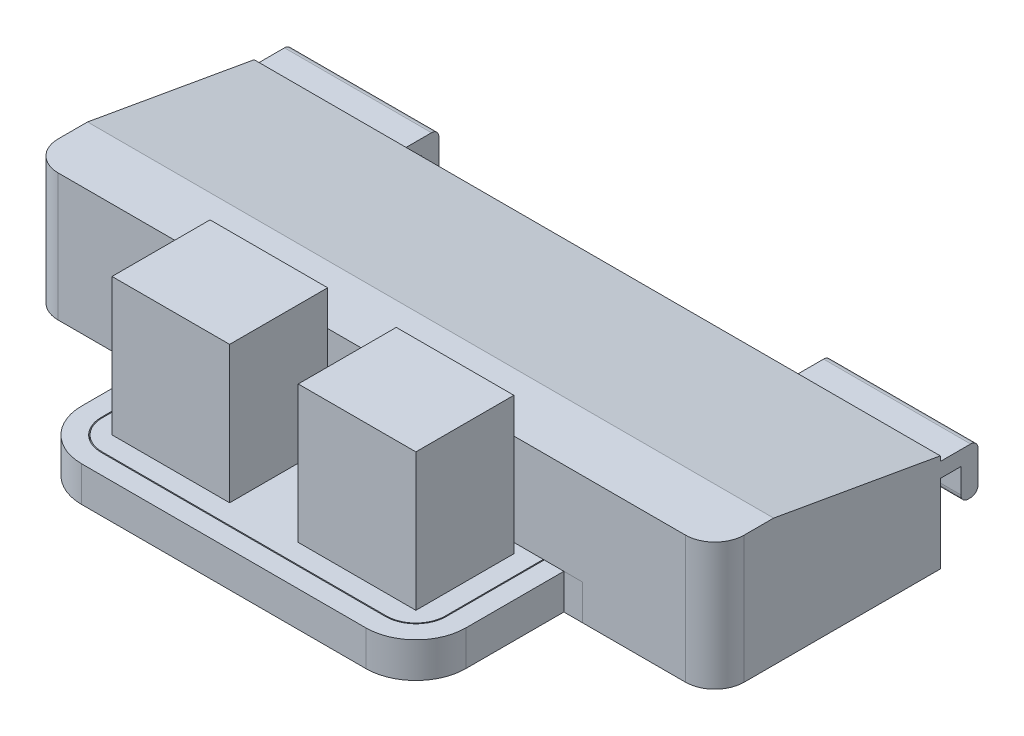
SolidWorks part; units mm, degrees
ref_plane "Front Plane" through (0, 0, 0) normal (0, 0, 1) x (1, 0, 0)
ref_plane "Top Plane" through (0, 0, 0) normal (0, 1, 0) x (1, 0, 0)
ref_plane "Right Plane" through (0, 0, 0) normal (1, 0, 0) x (0, 0, -1)
sketch "Sketch1" plane through (0, 0, 0) normal (0, 1, 0) x (1, 0, 0)
  line L0 (-17.5, 0) -> (-17.5, 15)
  line L1 (-17.5, 15) -> (-24.5, 15)
  line L2 (-24.5, 15) -> (-24.5, 30)
  line L3 (-24.5, 30) -> (24.5, 30)
  line L4 (24.5, 30) -> (24.5, 15)
  line L5 (24.5, 15) -> (17.5, 15)
  line L6 (17.5, 15) -> (17.5, 0)
  line L7 (17.5, 0) -> (-17.5, 0)
  line L8 (0, 0) -> (0, 30) construction
  point P2 (0, 0)
  dimension "D1" = 35
  dimension "D2" = 49
  dimension "D3" = 15
  dimension "D4" = 30
extrude "Boss-Extrude1" add sketch "Sketch1" along normal blind 1.6
sketch "Sketch2" plane through (0, 1.6, 0) normal (0, 1, 0) x (1, 0, 0)
  line L0 (0, 30) -> (0, 25.132) construction
  line L1 (24.5, 30) -> (-24.5, 30) construction
  line L2 (-24.5, 22.5) -> (-16.8448, 22.5) construction
  line L3 (-24.5, 30) -> (-24.5, 15) construction
  line L4 (-24.5, 15) -> (-17.5, 15) construction
  circle A0 centre (-20.5, 26) radius 1.5
  circle A1 centre (-20.5, 19) radius 1.5
  circle A2 centre (20.5, 26) radius 1.5
  circle A3 centre (20.5, 19) radius 1.5
  dimension "D1" = 3
  dimension "D2" = 4
  dimension "D3" = 4
extrude "Cut-Extrude1" cut sketch "Sketch2" against normal through all
fillet "Fillet1" radius 3 6 edges at (-17.5, 0.8, 0) (17.5, 0.8, 0) (24.5, 0.8, -15) (24.5, 0.8, -30) (-24.5, 0.8, -30) (-24.5, 0.8, -15)
sketch "Sketch3" plane through (0, 1.6, 0) normal (0, 1, 0) x (1, 0, 0)
  line L0 (0, 0) -> (0, 14.2709) construction
  line L1 (-14.5, 0) -> (14.5, 0) construction
  line L2 (15.5, 2) -> (3.5, 12) construction
  line L3 (-15.5, 12) -> (-3.5, 12)
  line L4 (-15.5, 12) -> (-15.5, 2)
  line L5 (-15.5, 2) -> (-3.5, 2)
  line L6 (-3.5, 12) -> (-3.5, 2)
  line L7 (-15.5, 12) -> (-3.5, 2) construction
  line L8 (-15.5, 2) -> (-3.5, 12) construction
  line L9 (15.5, 12) -> (3.5, 2) construction
  line L10 (3.5, 12) -> (3.5, 2)
  line L11 (15.5, 2) -> (3.5, 2)
  line L12 (15.5, 12) -> (15.5, 2)
  line L13 (15.5, 12) -> (3.5, 12)
  point P4 (-9.5, 7)
  point P13 (9.5, 7)
  dimension "D1" = 12
  dimension "D2" = 10
  dimension "D3" = 19
  dimension "D4" = 7
extrude "Boss-Extrude2" add sketch "Sketch3" along normal blind 14
sketch "Sketch4" plane through (0, 0, 0) normal (0, -1, 0) x (1, 0, 0)
  line L3 (0, -30) -> (0, -13) construction
  line L4 (-32, -13) -> (-19.6, -13)
  line L5 (-35, -16) -> (-35, -35)
  line L6 (19.6, -3) -> (19.6, -15)
  line L7 (-14.5, 2.1) -> (14.5, 2.1)
  line L8 (-19.6, -15) -> (-19.6, -3)
  line L9 (19.6, -3) -> (19.6, -13)
  line L10 (-14.5, 2.1) -> (14.5, 2.1)
  line L11 (-19.6, -13) -> (-19.6, -3)
  line L12 (-35, -35) -> (35, -35)
  line L13 (35, -16) -> (35, -35)
  line L14 (21.5, -30) -> (-21.5, -30) construction
  line L15 (-24.5, -27) -> (-24.5, -18) construction
  line L16 (-21.5, -15) -> (-17.5, -15) construction
  line L17 (19.6, -13) -> (32, -13)
  arc A2 (32, -13) -> (35, -16) centre (32, -16) cw
  arc A3 (-32, -13) -> (-35, -16) centre (-32, -16) ccw
  arc A4 (19.6, -3) -> (14.5, 2.1) centre (14.5, -3) ccw
  arc A5 (-14.5, 2.1) -> (-19.6, -3) centre (-14.5, -3) ccw
  arc A6 (19.6, -3) -> (14.5, 2.1) centre (14.5, -3) ccw
  arc A7 (-14.5, 2.1) -> (-19.6, -3) centre (-14.5, -3) ccw
  dimension "D5" = 3
  dimension "D2" = 10.5
  dimension "D3" = 2
  dimension "D4" = 5
  dimension "D6" = 70
  dimension "D1" = 2.1
extrude "Boss-Extrude3" add sketch "Sketch4" along normal blind 2 separate body
sketch "Sketch5" plane through (0, 0, 0) normal (0, 1, 0) x (1, 0, 0)
  line L8 (35, 16) -> (35, 35)
  line L9 (35, 35) -> (-35, 35)
  line L10 (-35, 35) -> (-35, 16)
  line L11 (-32, 13) -> (-19.6, 13)
  line L12 (-19.6, 13) -> (-19.6, 3)
  line L13 (-14.5, -2.1) -> (14.5, -2.1)
  line L14 (19.6, 3) -> (19.6, 13)
  line L15 (19.6, 13) -> (32, 13)
  line L19 (-21.5, 13) -> (-19.6, 13)
  line L20 (-19.6, 13) -> (-19.6, 3)
  line L21 (-14.5, -2.1) -> (14.5, -2.1)
  line L22 (19.6, 3) -> (19.6, 13)
  line L23 (19.6, 13) -> (21.5, 13)
  line L28 (-21.5, 14.9) -> (-21.5, 13)
  line L29 (21.5, 14.9) -> (21.5, 13)
  line L33 (-21.5, 14.9) -> (-17.6, 14.9)
  line L34 (17.6, 14.9) -> (21.5, 14.9)
  line L35 (-17.6, 14.9) -> (-17.6, 3)
  line L36 (-14.5, -0.1) -> (14.5, -0.1)
  line L37 (17.6, 3) -> (17.6, 14.9)
  line L38 (-21.5, 14.9) -> (-17.6, 14.9)
  line L39 (17.6, 14.9) -> (21.5, 14.9)
  line L40 (-17.6, 14.9) -> (-17.6, 3)
  line L41 (-14.5, -0.1) -> (14.5, -0.1)
  line L42 (17.6, 3) -> (17.6, 14.9)
  arc A4 (-35, 16) -> (-32, 13) centre (-32, 16) ccw
  arc A5 (-19.6, 3) -> (-14.5, -2.1) centre (-14.5, 3) ccw
  arc A6 (14.5, -2.1) -> (19.6, 3) centre (14.5, 3) ccw
  arc A7 (32, 13) -> (35, 16) centre (32, 16) ccw
  arc A9 (-19.6, 3) -> (-14.5, -2.1) centre (-14.5, 3) ccw
  arc A10 (14.5, -2.1) -> (19.6, 3) centre (14.5, 3) ccw
  arc A16 (-17.6, 3) -> (-14.5, -0.1) centre (-14.5, 3) ccw
  arc A17 (14.5, -0.1) -> (17.6, 3) centre (14.5, 3) ccw
  arc A18 (-17.6, 3) -> (-14.5, -0.1) centre (-14.5, 3) ccw
  arc A19 (14.5, -0.1) -> (17.6, 3) centre (14.5, 3) ccw
  dimension "D1" = 0
  dimension "D2" = 0.1
extrude "Boss-Extrude4" add sketch "Sketch5" along normal up to surface (1.6 mm away) separate body up to face at (-9.5, 1.6, -7)
sketch "Sketch6" plane through (0, 0, 0) normal (0, 1, 0) x (1, 0, 0)
  line L0 (-35, 16) -> (-35, 35) construction
  line L1 (-19.6, 13) -> (-32, 13) construction
  line L2 (32, 13) -> (19.6, 13) construction
  line L3 (35, 35) -> (35, 16) construction
  line L4 (-35, 16) -> (-35, 35)
  line L5 (-21.5, 13) -> (-32, 13)
  line L6 (32, 13) -> (21.5, 13)
  line L7 (35, 35) -> (35, 16)
  line L8 (-21.5, 14) -> (-32, 14)
  line L9 (-34, 16) -> (-34, 35)
  line L10 (34, 35) -> (34, 16)
  line L11 (32, 14) -> (21.5, 14)
  line L12 (-21.5, 13) -> (-21.5, 14.9) construction
  line L13 (21.5, 14.9) -> (21.5, 13) construction
  line L14 (-21.5, 13) -> (-21.5, 14)
  line L15 (21.5, 14) -> (21.5, 13)
  line L16 (35, 35) -> (34, 35)
  line L17 (-19.6, 13) -> (-32, 13) construction
  line L18 (-19.6, 14) -> (-32, 14) construction
  line L19 (32, 13) -> (19.6, 13) construction
  line L20 (32, 14) -> (19.6, 14) construction
  line L21 (-34, 35) -> (-35, 35)
  arc A0 (-35, 16) -> (-32, 13) centre (-32, 16) ccw construction
  arc A1 (32, 13) -> (35, 16) centre (32, 16) ccw construction
  arc A2 (-35, 16) -> (-32, 13) centre (-32, 16) ccw
  arc A3 (32, 13) -> (35, 16) centre (32, 16) ccw
  arc A4 (-34, 16) -> (-32, 14) centre (-32, 16) ccw
  arc A5 (32, 14) -> (34, 16) centre (32, 16) ccw
  dimension "D1" = 1
extrude "Cut-Extrude2" cut sketch "Sketch6" against normal through all
sketch "Sketch7" plane through (0, -2, 0) normal (0, -1, 0) x (1, 0, 0)
  line L5 (-34, -16) -> (-34, -35) construction
  line L6 (-21.5, -14) -> (-32, -14) construction
  line L7 (-34, -35) -> (34, -35) construction
  line L8 (34, -35) -> (34, -16) construction
  line L9 (32, -14) -> (21.5, -14) construction
  line L10 (-21.5, -13) -> (-32, -13)
  line L11 (-35, -16) -> (-35, -36)
  line L12 (-35, -36) -> (35, -36)
  line L13 (32, -13) -> (21.5, -13)
  line L14 (35, -36) -> (35, -16)
  line L15 (-21.5, -13) -> (-32, -13)
  line L16 (-35, -16) -> (-35, -36)
  line L17 (-35, -36) -> (35, -36)
  line L18 (32, -13) -> (21.5, -13)
  line L19 (35, -36) -> (35, -16)
  line L20 (-34, -16) -> (-34, -35)
  line L21 (-21.5, -14) -> (-32, -14)
  line L22 (-34, -35) -> (34, -35)
  line L23 (34, -35) -> (34, -16)
  line L24 (32, -14) -> (21.5, -14)
  line L25 (21.5, -14) -> (21.5, -13)
  line L26 (-21.5, -14) -> (-21.5, -13)
  arc A2 (-32, -14) -> (-34, -16) centre (-32, -16) ccw construction
  arc A3 (34, -16) -> (32, -14) centre (32, -16) ccw construction
  arc A4 (-32, -13) -> (-35, -16) centre (-32, -16) ccw
  arc A5 (35, -16) -> (32, -13) centre (32, -16) ccw
  arc A6 (-32, -13) -> (-35, -16) centre (-32, -16) ccw
  arc A7 (35, -16) -> (32, -13) centre (32, -16) ccw
  arc A8 (-32, -14) -> (-34, -16) centre (-32, -16) ccw
  arc A9 (34, -16) -> (32, -14) centre (32, -16) ccw
  dimension "D1" = 1
extrude "Boss-Extrude5" add sketch "Sketch7" against normal blind 15 separate body
sketch "Sketch8" plane through (0, 0, 0) normal (1, 0, 0) x (0, 0, -1)
  line L0 (36, 8) -> (19, 11)
  line L1 (36, 13) -> (36, -2) construction
  line L2 (19, 11) -> (13, 11)
  line L3 (13, 13) -> (13, -2) construction
  line L4 (13, 11) -> (13, 13)
  line L5 (13, 13) -> (36, 13)
  line L6 (36, 13) -> (36, 8)
  line L7 (16, -2) -> (36, -2) construction
  dimension "D1" = 10
  dimension "D2" = 2
  dimension "D3" = 6
extrude "Cut-Extrude3" cut sketch "Sketch8" against normal through all both and the other way through all
sketch "Sketch9" plane through (0, 0, 0) normal (1, 0, 0) x (0, 0, -1)
  line L0 (35, 8.1765) -> (19, 11)
  line L1 (19, 11) -> (14, 11)
  line L2 (14, 11) -> (14, 9.46)
  line L3 (14, 11) -> (14, -2) construction
  line L4 (14, 9.46) -> (19.0953, 9.46)
  line L5 (19.0953, 9.46) -> (35, 6.6533)
  line L6 (35, 8.1765) -> (35, -2) construction
  line L7 (35, 6.6533) -> (35, 8.1765)
  dimension "D1" = 1.54
  dimension "D2" = 1.5
extrude "Boss-Extrude6" add sketch "Sketch9" along normal up to next and the other way up to next
sketch "Sketch10" plane through (0, 11, 0) normal (0, 1, 0) x (1, 0, 0)
  line L1 (21.5, 13) -> (-21.5, 13)
  line L2 (21.5, 13) -> (21.5, 14)
  line L3 (21.5, 14) -> (-21.5, 14)
  line L4 (-21.5, 13) -> (-21.5, 14)
  line L5 (-21.5, 14) -> (21.5, 14) construction
  line L6 (-21.5, 13) -> (-21.5, 14) construction
extrude "Boss-Extrude7" add sketch "Sketch10" against normal up to surface (9.4 mm away) separate body up to face at (-9.5, 1.6, -7)
sketch "Sketch11" plane through (0, 0, -36) normal (0, 0, -1) x (-1, 0, 0)
  line L0 (-20, 1.6) -> (20, 1.6) construction
  line L1 (-21.5, 1.6) -> (21.5, 1.6) construction
  line L2 (-20, 3.2) -> (20, 3.2)
  line L3 (-20, 0) -> (20, 0)
  line L4 (34, 0) -> (-34, 0) construction
  arc A0 (-20, 3.2) -> (-20, 0) centre (-20, 1.6) ccw
  arc A1 (20, 0) -> (20, 3.2) centre (20, 1.6) ccw
  point P4 (0, 1.6)
  dimension "D1" = 3.2
  dimension "D2" = 40
extrude "Cut-Extrude4" cut sketch "Sketch11" against normal up to next (1 mm away)
sketch "Sketch12" plane through (-35, 0, 0) normal (-1, 0, 0) x (0, 0, 1)
  line L0 (-36, 7.5) -> (-39.1, 7.5)
  line L1 (-39.85, 6.75) -> (-39.85, 3.5)
  line L2 (-39.1, 2.75) -> (-38.85, 2.75)
  line L3 (-38.1, 3.5) -> (-38.1, 6)
  line L4 (-38.1, 6) -> (-36, 6)
  line L5 (-36, 8) -> (-36, -2) construction
  line L6 (-16, -2) -> (-36, -2) construction
  line L7 (-36, 6) -> (-36, 7.5)
  arc A0 (-39.1, 7.5) -> (-39.85, 6.75) centre (-39.1, 6.75) ccw
  arc A1 (-38.85, 2.75) -> (-38.1, 3.5) centre (-38.85, 3.5) ccw
  arc A2 (-39.85, 3.5) -> (-39.1, 2.75) centre (-39.1, 3.5) ccw
  point P16 (-39.85, 7.5)
  point P19 (-38.1, 2.75)
  point P22 (-39.85, 2.75)
  dimension "D8" = 0.75
  dimension "D1" = 3.85
  dimension "D2" = 1.75
  dimension "D3" = 2.1
  dimension "D4" = 3.25
  dimension "D5" = 2.1
  dimension "D6" = 8
  dimension "D7" = 1.5
extrude "Boss-Extrude8" add sketch "Sketch12" against normal blind 15 contours L1 A2 L2 A1 L3 L4 L7 L0 A0
mirror "Mirror1" about plane through (0, 0, 0) normal (1, 0, 0) of "Boss-Extrude8"
combine bodies "Combine1" operation type add bodies to combine 118 115
combine bodies "Combine2" operation type add bodies to combine 111 110
